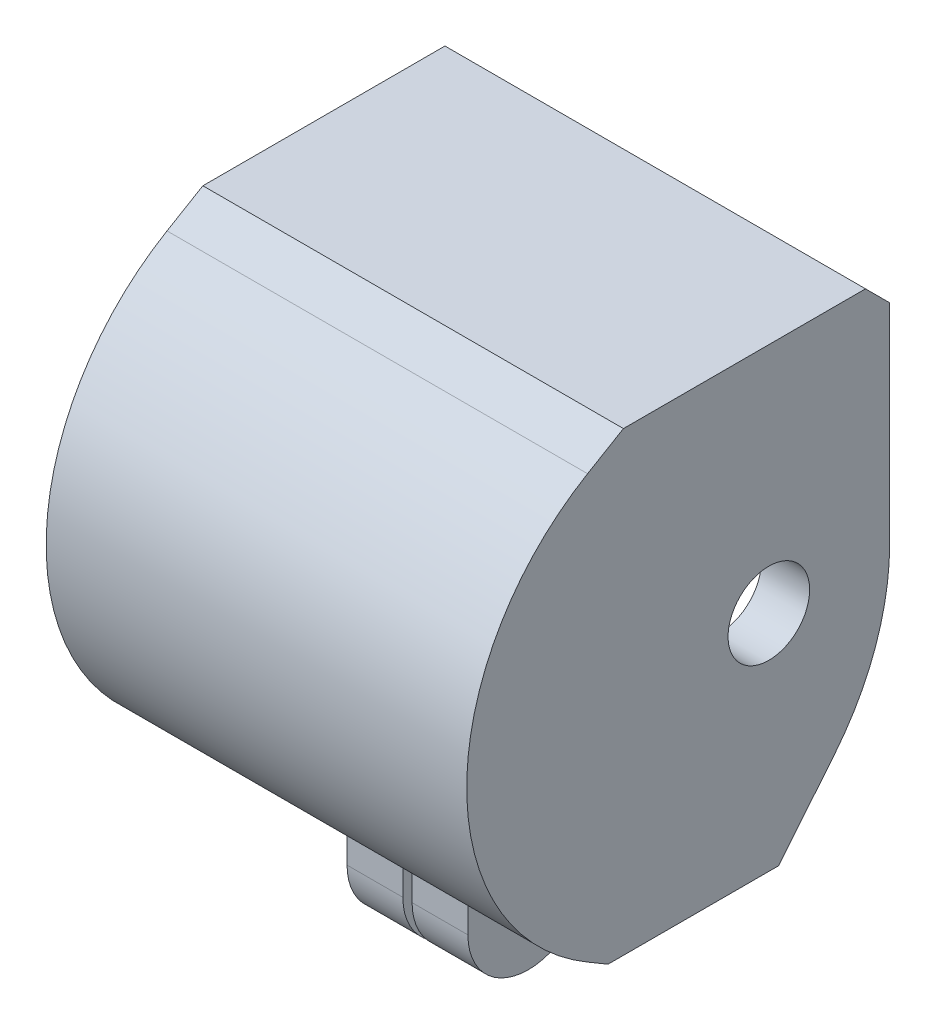
SolidWorks part; units mm, degrees
ref_plane "Front Plane" through (0, 0, 0) normal (0, 0, 1) x (1, 0, 0)
ref_plane "Top Plane" through (0, 0, 0) normal (0, 1, 0) x (1, 0, 0)
ref_plane "Right Plane" through (0, 0, 0) normal (1, 0, 0) x (0, 0, -1)
sketch "Sketch1" plane through (0, 0, 0) normal (1, 0, 0) x (0, 0, -1)
  line L0 (0, 17.5) -> (0, -17.5) construction
  line L1 (0, 17.5) -> (-15, 17.5)
  line L2 (10, 17.5) -> (10, -17.5) construction
  line L3 (0, -17.5) -> (-15, -17.5)
  line L4 (-15, 17.5) -> (-15, -17.5) construction
  line L5 (0, 0) -> (10, 0) construction
  line L6 (0, 0) -> (-10, 0) construction
  line L7 (0, 0) -> (-10, 0) construction
  line L8 (-15, 0) -> (-25, 0) construction
  arc A0 (0, -17.5) -> (0, 17.5) centre (-10.3125, 0) ccw
  arc A1 (-15, 17.5) -> (-15, -17.5) centre (-4.6875, 0) ccw
  dimension "D3" = 25
  dimension "D1" = 35
extrude "Boss-Extrude1" add sketch "Sketch1" against normal mid plane 34.8
sketch "Sketch2" plane through (0, 0, 0) normal (1, 0, 0) x (0, 0, -1)
  line L0 (0, 17.5) -> (-15, 17.5) construction
  line L1 (-15, -17.5) -> (0, -17.5) construction
  line L2 (-17, 0) -> (-25, 0) construction
  line L4 (-15, -17.5) -> (0, -17.5)
  line L5 (0, 17.5) -> (-15, 17.5)
  line L6 (-7, -17.5) -> (0, -17.5)
  line L7 (0, 17.5) -> (-7, 17.5)
  arc A0 (-7, 17.5) -> (-7, -17.5) centre (3.3125, 0) ccw
  arc A1 (-15, 17.5) -> (-15, -17.5) centre (-4.6875, 0) ccw construction
  arc A4 (-15, 17.5) -> (-15, -17.5) centre (-4.6875, 0) ccw
  arc A5 (0, -17.5) -> (0, 17.5) centre (-10.3125, 0) ccw
  arc A7 (0, -17.5) -> (0, 17.5) centre (-10.3125, 0) ccw
  dimension "D1" = 0
  dimension "D2" = 8
extrude "Cut-Extrude1" cut sketch "Sketch2" along normal mid plane 26.8
sketch "Sketch3" plane through (0, 0, 0) normal (1, 0, 0) x (0, 0, -1)
  line L0 (-12.5, -17.5) -> (-12.5, -23)
  line L1 (-15, -17.5) -> (0, -17.5) construction
  line L2 (-2.5, -23) -> (-2.5, -17.5)
  line L3 (-2.5, -17.5) -> (-12.5, -17.5)
  line L4 (-7.5, -28) -> (-7.5, -17.5) construction
  arc A0 (-12.5, -23) -> (-2.5, -23) centre (-7.5, -23) ccw
  dimension "D1" = 10
  dimension "D2" = 5.5
extrude "Boss-Extrude2" add sketch "Sketch3" along normal mid plane 10
sketch "Sketch4" plane through (17.4, 0, 0) normal (1, 0, 0) x (0, 0, -1)
  line L0 (-14.8742, -9.0466) -> (0.9816, -18.201)
  line L1 (0.8089, -18.5) -> (-13.303, -18.5)
  line L4 (-14.8742, -9.0466) -> (-22.8742, -9.0466)
  line L5 (0.8089, -18.5) -> (0.9816, -18.201)
  line L8 (0, 0) -> (14.9634, 0.0217) construction
  line L9 (14.9634, 0.0217) -> (14.9855, -15.25) construction
  line L10 (69.9999, 0.1014) -> (0, 0) construction
  line L12 (-15, -17.5) -> (-13.303, -18.5)
  line L13 (0.9816, -18.201) -> (8.6174, -4.9753) construction
  line L14 (0, 0) -> (8.6174, -4.9753) construction
  line L15 (0, 0) -> (-8.348, 0) construction
  line L16 (-15, -17.5) -> (0, -17.5) construction
  arc A0 (-15, 17.5) -> (-15, -17.5) centre (-4.6875, 0) ccw construction
  arc A2 (-7, 17.5) -> (-7, -17.5) centre (3.3125, 0) ccw construction
  arc A3 (-7, 17.5) -> (-7, -17.5) centre (3.3125, 0) ccw construction
  arc A4 (-22.8742, -9.0466) -> (-15, -17.5) centre (-4.6875, 0) ccw
  point P4 (13.3348, -15.2224)
  point P5 (0, 0)
  dimension "D1" = 30
  dimension "D2" = 0.299
  dimension "D3" = 1
extrude "Boss-Extrude3" add sketch "Sketch4" against normal up to surface (34.8 mm away) up to face at (-17.4, 0, 7.5)
sketch "Sketch5" plane through (17.4, 0, 0) normal (1, 0, 0) x (0, 0, -1)
  line L4 (-13.303, -18.5) -> (0.8089, -18.5) construction
  line L5 (5.426, -12.8412) -> (0.8089, -18.5)
  line L6 (0.8089, -18.5) -> (0.9816, -18.201) construction
  line L7 (0.8089, -18.5) -> (-1.1911, -18.5)
  line L8 (-1.1911, -18.5) -> (-1.1911, -17.5)
  line L9 (-1.1911, -17.5) -> (5.426, -12.8412)
  arc A3 (0, -17.5) -> (0, 17.5) centre (-10.3125, 0) ccw construction
  dimension "D1" = 1
  dimension "D2" = 2
extrude "Boss-Extrude4" add sketch "Sketch5" against normal up to surface (4 mm away) up to face at (13.4, -1.4994, 3.4662)
sketch "Sketch6" plane through (-17.4, 0, 0) normal (-1, 0, 0) x (0, 0, 1)
  line L2 (-5.426, -12.8412) -> (-0.8089, -18.5)
  line L3 (-5.426, -12.8412) -> (-0.8089, -18.5)
  line L4 (-0.8089, -18.5) -> (1.1911, -18.5)
  line L5 (-0.8089, -18.5) -> (1.1911, -18.5)
  line L12 (1.1911, -18.5) -> (1.1911, -17.5)
  line L13 (1.1911, -18.5) -> (1.1911, -17.5)
  line L14 (1.1911, -17.5) -> (-5.426, -12.8412)
  line L15 (1.1911, -17.5) -> (-5.426, -12.8412)
  dimension "D1" = 0
extrude "Boss-Extrude5" add sketch "Sketch6" against normal up to surface (4 mm away) up to face at (-13.4, -1.4994, 3.4662)
sketch "Sketch7" plane through (17.4, 0, 0) normal (1, 0, 0) x (0, 0, -1)
  line L0 (-15, 17.5) -> (-12.032, 19.249)
  line L1 (-12.032, 19.249) -> (10, 19.249)
  line L2 (10, 19.249) -> (10, 15.249)
  line L3 (0, 0) -> (0.6988, 0.001) construction
  line L4 (10, 15.249) -> (-18.1064, 15.249)
  line L6 (0, 0) -> (0, 15.249) construction
  line L7 (0.6988, 0.001) -> (0.6767, 15.25) construction
  line L9 (69.9999, 0.1014) -> (0, 0) construction
  line L11 (26.781, 15.25) -> (85.38, 15.25) construction
  arc A0 (-15, 17.5) -> (-15, -17.5) centre (-4.6875, 0) ccw construction
  arc A1 (-15, 17.5) -> (-18.1064, 15.249) centre (-4.6875, 0) ccw
  arc A2 (5.426, -12.8412) -> (0, 17.5) centre (-10.3125, 0) ccw construction
  dimension "D2" = 4
extrude "Boss-Extrude6" add sketch "Sketch7" against normal up to surface (34.8 mm away) up to face at (-17.4, -5.1825, 6.6831)
sketch "Sketch8" plane through (17.4, 0, 0) normal (1, 0, 0) x (0, 0, -1)
  line L0 (10, 15.249) -> (10, 0)
  line L1 (3.1064, 15.249) -> (10, 15.249) construction
  line L2 (3.1064, 15.249) -> (10, 15.249)
  arc A0 (5.426, -12.8412) -> (3.1064, 15.249) centre (-10.3125, 0) ccw construction
  arc A1 (10, 0) -> (3.1064, 15.249) centre (-10.3125, 0) ccw
extrude "Boss-Extrude7" add sketch "Sketch8" against normal up to surface (4 mm away) up to face at (13.4, -4.4688, 2.187)
sketch "Sketch9" plane through (-17.4, 0, 0) normal (-1, 0, 0) x (0, 0, 1)
  line L2 (-10, 15.249) -> (-10, 0)
  line L3 (-3.1064, 15.249) -> (-10, 15.249)
  line L4 (-10, 15.249) -> (-10, 0)
  line L5 (-3.1064, 15.249) -> (-10, 15.249)
  arc A1 (-3.1064, 15.249) -> (-10, 0) centre (10.3125, 0) ccw
  arc A2 (-3.1064, 15.249) -> (-10, 0) centre (10.3125, 0) ccw
  dimension "D1" = 0
extrude "Boss-Extrude8" add sketch "Sketch9" against normal up to surface (4 mm away) up to face at (-13.4, -4.4688, 2.187)
chamfer "Chamfer2" distance 2 angle 45 1 edges at (0, 19.249, -10)
sketch "Sketch10" plane through (17.4, 0, 0) normal (1, 0, 0) x (0, 0, -1)
  circle A0 centre (0, 0) radius 3.175 construction
  circle A1 centre (0, 0) radius 3.375
  dimension "D1" = 6.35
  dimension "D2" = 0.2
extrude "Cut-Extrude2" cut sketch "Sketch10" against normal through all
sketch "Sketch11" plane through (0, 0, 0) normal (1, 0, 0) x (0, 0, -1)
  line L3 (-12.5, -17.5) -> (-12.5, -23)
  line L4 (-2.5, -23) -> (-2.5, -17.5)
  line L5 (-2.5, -17.5) -> (-12.5, -17.5)
  line L6 (-12.5, -17.5) -> (-12.5, -23)
  line L7 (-2.5, -23) -> (-2.5, -17.5)
  line L8 (-2.5, -17.5) -> (-12.5, -17.5)
  arc A1 (-12.5, -23) -> (-2.5, -23) centre (-7.5, -23) ccw
  arc A2 (-12.5, -23) -> (-2.5, -23) centre (-7.5, -23) ccw
  dimension "D1" = 0
extrude "Cut-Extrude3" cut sketch "Sketch11" against normal mid plane 0.762
